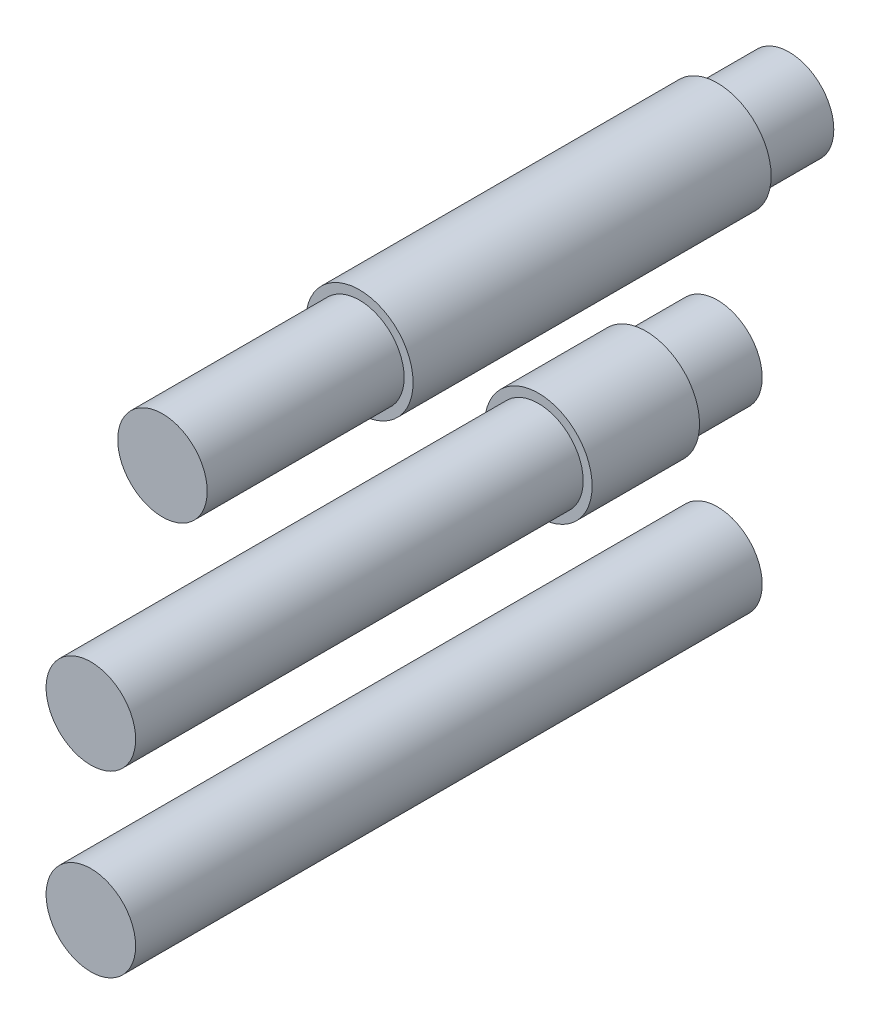
SolidWorks part; units mm, degrees
ref_plane "Plano frontal" through (0, 0, 0) normal (0, 0, 1) x (1, 0, 0)
ref_plane "Plano superior" through (0, 0, 0) normal (0, 1, 0) x (1, 0, 0)
ref_plane "Plano direito" through (0, 0, 0) normal (1, 0, 0) x (0, 0, -1)
sketch "Esboço1" plane through (0, 0, 0) normal (0, 0, 1) x (1, 0, 0)
  circle A0 centre (-5.7545, 0.7925) radius 1.25
  circle A1 centre (-5.7545, 0.7925) radius 1.5
  circle A2 centre (-0.7545, 0.7925) radius 1.25
  circle A3 centre (-0.7545, 0.7925) radius 1.5
  circle A4 centre (4.2455, 0.7925) radius 1.25
  circle A5 centre (4.2455, 0.7925) radius 1.5
  dimension "D1" = 2.5
  dimension "D2" = 3
  dimension "D3" = 3
extrude "Ressalto-extrusão1" add sketch "Esboço1" along normal blind 5.5 and the other way blind 12 contours A0 region at (-5.7545, 0.7925, 0)
extrude "Ressalto-extrusão2" add sketch "Esboço1<4>" along normal blind 12.5 and the other way blind 5 separate body contours A2 region at (-0.7545, 0.7925, 0)
sketch "Esboço1<4>" plane through (0, 0, 0) normal (0, 0, 1) x (1, 0, 0) same geometry as "Esboço1"
sketch "Esboço2" plane through (0, 0, 0) normal (0, 0, 1) x (1, 0, 0)
  circle A0 centre (-5.7545, 0.7925) radius 1.25
  circle A1 centre (-5.7545, 0.7925) radius 1.5
  circle A2 centre (-0.7545, 0.7925) radius 1.25
  circle A3 centre (-0.7545, 0.7925) radius 1.5
  circle A4 centre (4.2455, 0.7925) radius 1.25
  circle A5 centre (4.2455, 0.7925) radius 1.5
  point P4 (0, 0)
  dimension "D1" = 2.5
  dimension "D2" = 3
  dimension "D3" = 3
extrude "Ressalto-extrusão3" add sketch "Esboço2" along normal blind 17.5 separate body contours A4
sketch "Esboço6" plane through (0, 0, 0) normal (0, 0, 1) x (1, 0, 0)
  circle A0 centre (-5.7545, 0.7925) radius 1.25
  circle A1 centre (-5.7545, 0.7925) radius 1.5
  circle A2 centre (-0.7545, 0.7925) radius 1.25
  circle A3 centre (-0.7545, 0.7925) radius 1.5
  circle A4 centre (4.2455, 0.7925) radius 1.25
  circle A5 centre (4.2455, 0.7925) radius 1.5
  dimension "D1" = 2.5
  dimension "D2" = 3
  dimension "D3" = 3
extrude "Ressalto-extrusão4" add sketch "Esboço6" against normal blind 10 contours A1
sketch "Esboço7" plane through (0, 0, 0) normal (0, 0, 1) x (1, 0, 0)
  circle A0 centre (-5.7545, 0.7925) radius 1.25
  circle A1 centre (-5.7545, 0.7925) radius 1.5
  circle A2 centre (-0.7545, 0.7925) radius 1.25
  circle A3 centre (-0.7545, 0.7925) radius 1.5
  circle A4 centre (4.2455, 0.7925) radius 1.25
  circle A5 centre (4.2455, 0.7925) radius 1.5
  dimension "D1" = 2.5
  dimension "D2" = 3
  dimension "D3" = 3
extrude "Ressalto-extrusão5" add sketch "Esboço7" against normal blind 3 separate body contours A3
